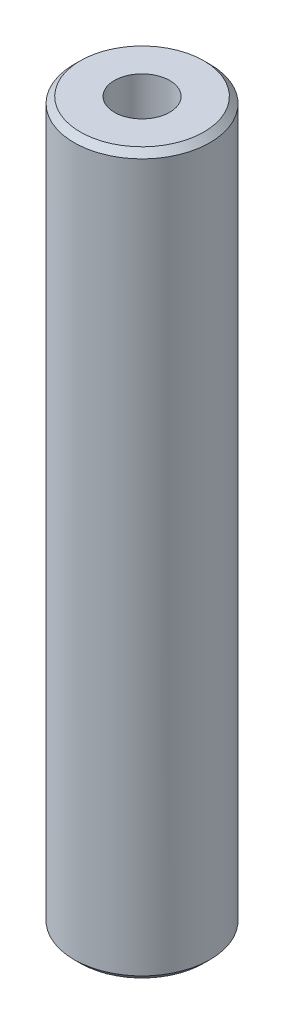
SolidWorks part; units mm, degrees
ref_plane "Front Plane" through (0, 0, 0) normal (0, 0, 1) x (1, 0, 0)
ref_plane "Top Plane" through (0, 0, 0) normal (0, 1, 0) x (1, 0, 0)
ref_plane "Right Plane" through (0, 0, 0) normal (1, 0, 0) x (0, 0, -1)
sketch "Sketch1" plane through (0, 0, 0) normal (0, 1, 0) x (1, 0, 0)
  circle A0 centre (0, 0) radius 55
  dimension "SHAFT_OD" = 110
extrude "Boss-Extrude1" add sketch "Sketch1" along normal blind 582.9458
sketch "Sketch2" plane through (0, 0, 0) normal (0, 1, 0) x (1, 0, 0)
  circle A0 centre (0, 0) radius 22.3731
  dimension "BORE_D" = 44.7463
extrude "Cut-Extrude1" cut sketch "Sketch2" along normal through all
chamfer "Chamfer1" distance 4.9775 angle 45 2 edges at (0, 582.9458, 55) (0, 0, 55)
